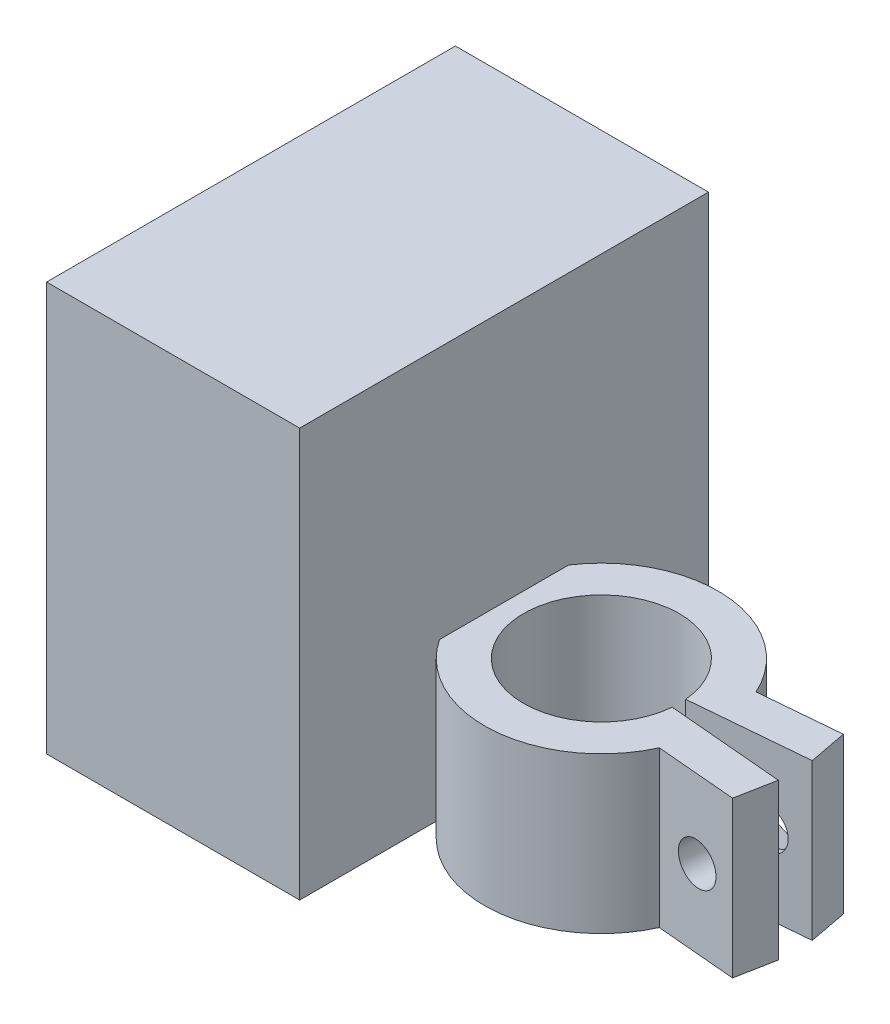
SolidWorks part; units mm, degrees
ref_plane "Front Plane" through (0, 0, 0) normal (0, 0, 1) x (1, 0, 0)
ref_plane "Top Plane" through (0, 0, 0) normal (0, 1, 0) x (1, 0, 0)
ref_plane "Right Plane" through (0, 0, 0) normal (1, 0, 0) x (0, 0, -1)
sketch "Sketch1" plane through (0, 0, 0) normal (0, 1, 0) x (1, 0, 0)
  line L1 (0, 0) -> (31.6292, -2.7672)
  line L2 (0, 0) -> (31.6292, 2.7672)
  line L3 (30.4367, -9.0371) -> (17.3387, -7.8912)
  line L4 (0, 0) -> (19.05, 0) construction
  line L5 (30.4367, 9.0371) -> (17.3387, 7.8912)
  line L7 (31.6292, 2.7672) -> (30.4367, 9.0371)
  line L8 (30.4367, -9.0371) -> (31.6292, -2.7672)
  line L9 (17.3387, -7.8912) -> (18.9775, -1.6603)
  line L10 (18.9775, 1.6603) -> (17.3387, 7.8912)
  circle A0 centre (0, 0) radius 12.7
  circle A1 centre (0, 0) radius 19.05
  circle A2 centre (0, 0) radius 31.75 construction
  dimension "D1" = 25.4
  dimension "D2" = 6.35
  dimension "D5" = 5
  dimension "D3" = 12.7
  dimension "D4" = 6.35
  dimension "D6" = 5
extrude "Boss-Extrude1" add sketch "Sketch1" along normal blind 25.4 contours L10 A1 L9 L1 A0 L2 | A1 L2 L7 L5 | A1 L3 L8 L1 | L9 A1 | L10 A1 region at (17.6375, 0, 4.6388) region at (18.2643, 0, 4.8037) region at (24.6837, 0, 5.3651) region at (18.2643, 0, -4.8037) region at (24.6837, 0, -5.3651)
sketch "Sketch3" plane through (-0.5534, 0, 6.3258) normal (-0.0872, 0, 0.9962) x (0.9962, 0, 0.0872)
  line L0 (31.1085, 25.4) -> (31.1085, 0) construction
  line L1 (31.1085, 25.4) -> (17.9605, 25.4) construction
  circle A0 centre (24.7585, 12.7) radius 3.3734
  dimension "D1" = 6.7469
  dimension "D2" = 6.35
  dimension "D3" = 12.7
sketch "Sketch4" plane through (-0.5534, 0, -6.3258) normal (-0.0872, 0, -0.9962) x (-0.9962, 0, 0.0872)
  line L0 (-31.1085, 25.4) -> (-31.1085, 0) construction
  line L1 (-31.1085, 25.4) -> (-17.9605, 25.4) construction
  circle A0 centre (-24.7585, 12.7) radius 3.3734
  point P6 (-22.813, 25.4)
  dimension "D3" = 6.7469
  dimension "D1" = 6.35
  dimension "D2" = 12.7
extrude "Cut-Extrude1" cut sketch "Sketch3" against normal up to next
extrude "Cut-Extrude2" cut sketch "Sketch4" against normal up to next
sketch "Sketch6" plane through (0, 0, 0) normal (0, -1, 0) x (1, 0, 0)
  line L0 (-19.05, -30.1625) -> (-19.05, 30.1625)
  line L1 (-15.875, -33.3375) -> (-57.15, -33.3375)
  line L2 (-15.875, -33.3375) -> (-15.875, 33.3375)
  line L3 (-15.875, 33.3375) -> (-57.15, 33.3375)
  line L4 (-57.15, -33.3375) -> (-57.15, 33.3375)
  line L5 (-19.05, 30.1625) -> (-53.975, 30.1625)
  line L6 (-53.975, -30.1625) -> (-53.975, 30.1625)
  line L7 (-19.05, -30.1625) -> (-53.975, -30.1625)
  arc A2 (17.3387, 7.8912) -> (17.3387, -7.8912) centre (0, 0) ccw construction
  point P8 (-19.05, 0)
  dimension "D2" = 60.325
  dimension "D3" = 34.925
  dimension "D1" = 3.175
extrude "Boss-Extrude4" add sketch "Sketch6" against normal blind 63.5
sketch "Sketch7" plane through (0, 63.5, 0) normal (0, 1, 0) x (1, 0, 0)
  line L4 (-15.875, -33.3375) -> (-15.875, 33.3375)
  line L5 (-15.875, 33.3375) -> (-57.15, 33.3375)
  line L6 (-57.15, 33.3375) -> (-57.15, -33.3375)
  line L7 (-57.15, -33.3375) -> (-15.875, -33.3375)
  line L8 (-15.875, -33.3375) -> (-15.875, 33.3375)
  line L9 (-15.875, 33.3375) -> (-57.15, 33.3375)
  line L10 (-57.15, 33.3375) -> (-57.15, -33.3375)
  line L11 (-57.15, -33.3375) -> (-15.875, -33.3375)
  dimension "D1" = 0
extrude "Boss-Extrude5" add sketch "Sketch7" along normal blind 3.175
fillet "Fillet1" radius 5 1 edges at (-19.05, 63.5, 0) second distance 10 first distance on face at (-19.05, 31.75, 0)
fillet "Fillet2" radius 10 1 edges at (-53.975, 63.5, 0) second distance 20 first distance on face at (-53.975, 31.75, 0)
sketch "Sketch8" plane through (-0.5534, 0, -6.3258) normal (-0.0872, 0, -0.9962) x (-0.9962, 0, 0.0872)
  line L1 (-19.1959, 9.4884) -> (-19.1959, 15.9116)
  line L2 (-19.1959, 15.9116) -> (-24.7585, 19.1231)
  line L3 (-24.7585, 19.1231) -> (-30.3211, 15.9116)
  line L4 (-30.3211, 15.9116) -> (-30.3211, 9.4884)
  line L5 (-30.3211, 9.4884) -> (-24.7585, 6.2769)
  line L6 (-24.7585, 6.2769) -> (-19.1959, 9.4884)
  circle A0 centre (-24.7585, 12.7) radius 5.5626 construction
  dimension "D1" = 11.1252
extrude "Cut-Extrude3" cut sketch "Sketch8" against normal blind 5.08 draft 4.3
